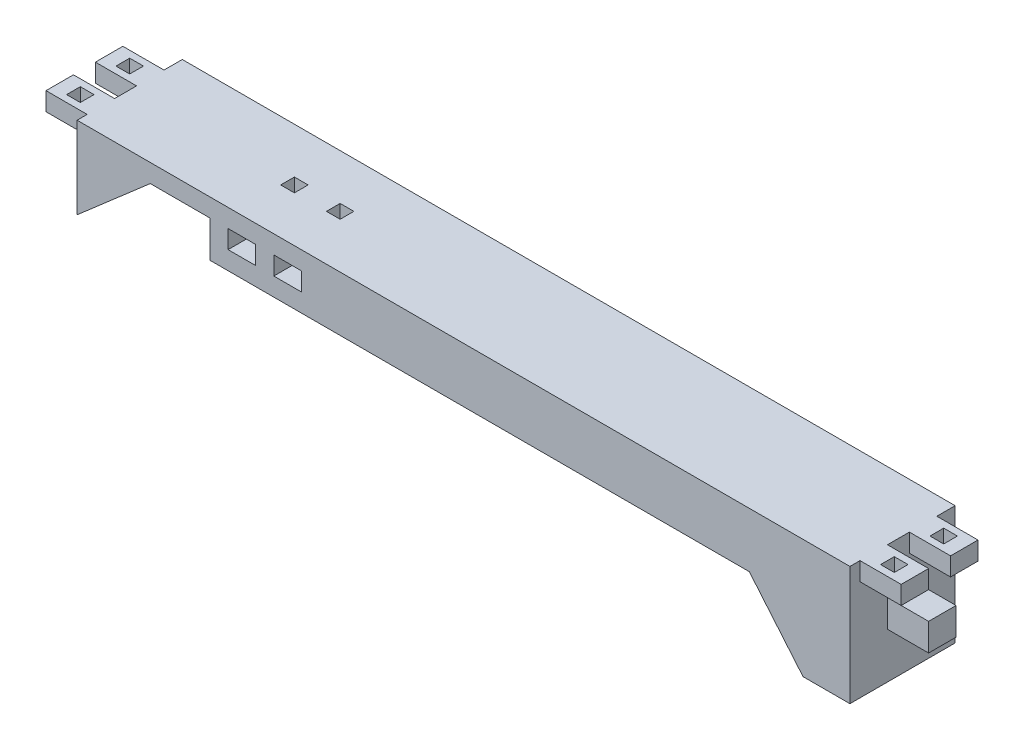
SolidWorks part; units mm, degrees
ref_plane "Front Plane" through (0, 0, 0) normal (0, 0, 1) x (1, 0, 0)
ref_plane "Top Plane" through (0, 0, 0) normal (0, 1, 0) x (1, 0, 0)
ref_plane "Right Plane" through (0, 0, 0) normal (1, 0, 0) x (0, 0, -1)
sketch "Sketch1" plane through (0, 0, 0) normal (0, 1, 0) x (1, 0, 0)
  line L1 (0, 0) -> (186.97, 0)
  line L2 (0, 0) -> (0, 23)
  line L3 (0, 23) -> (186.97, 23)
  line L4 (186.97, 0) -> (186.97, 23)
  dimension "D1" = 23
  dimension "D2" = 186.97
extrude "Boss-Extrude1" add sketch "Sketch1" along normal blind 4
sketch "Sketch2" plane through (0, 0, 0) normal (0, -1, 0) x (1, 0, 0)
  line L0 (186.97, -23) -> (0, -23) construction
  line L1 (177.97, 0) -> (167.97, 0)
  line L2 (177.97, 0) -> (177.97, -23)
  line L3 (177.97, -23) -> (167.97, -23)
  line L4 (167.97, 0) -> (167.97, -23)
  point P7 (0, 0)
  dimension "D1" = 10
extrude "Boss-Extrude2" add sketch "Sketch2" along normal blind 22
sketch "Sketch3" plane through (0, 0, 0) normal (0, -1, 0) x (1, 0, 0)
  line L0 (167.97, 0) -> (167.97, -23) construction
  line L1 (167.97, 0) -> (38.01, 0)
  line L2 (167.97, 0) -> (167.97, -8)
  line L3 (167.97, -8) -> (62.01, -8)
  line L4 (38.01, 0) -> (38.01, -8)
  line L5 (167.97, -23) -> (0, -23) construction
  line L7 (38.01, -8) -> (38.01, -23)
  line L8 (38.01, -23) -> (62.01, -23)
  line L9 (62.01, -8) -> (62.01, -23)
  dimension "D1" = 129.96
  dimension "D2" = 8
  dimension "D3" = 24
extrude "Boss-Extrude3" add sketch "Sketch3" along normal blind 8
chamfer "Chamfer1" distance 12 angle 50 1 edges at (167.97, -8, -4) first distance on face at (89.33, -8, -10.3333)
sketch "Sketch4" plane through (0, 0, 0) normal (0, -1, 0) x (1, 0, 0)
  line L6 (186.97, 0) -> (186.97, -23) construction
  line L11 (186.97, -8.2) -> (177.97, -8.2)
  line L12 (186.97, -8.2) -> (186.97, -13)
  line L13 (186.97, -13) -> (177.97, -13)
  line L14 (177.97, -8.2) -> (177.97, -13)
  line L15 (177.97, -23) -> (177.97, 0) construction
  line L17 (186.97, -23) -> (177.97, -23) construction
  line L18 (0, -23) -> (0, 0) construction
  line L19 (186.97, -23) -> (177.97, -23)
  line L20 (186.97, -23) -> (186.97, -19)
  line L21 (186.97, -19) -> (177.97, -19)
  line L22 (177.97, -23) -> (177.97, -19)
  line L23 (186.97, 0) -> (177.97, 0)
  line L24 (186.97, 0) -> (186.97, -2.2)
  line L25 (186.97, -2.2) -> (177.97, -2.2)
  line L26 (177.97, 0) -> (177.97, -2.2)
  line L27 (180.97, -14.5) -> (183.97, -14.5)
  line L28 (180.97, -14.5) -> (180.97, -17.5)
  line L29 (180.97, -17.5) -> (183.97, -17.5)
  line L30 (183.97, -14.5) -> (183.97, -17.5)
  line L31 (180.97, -3.7) -> (183.97, -3.7)
  line L32 (180.97, -3.7) -> (180.97, -6.7)
  line L33 (180.97, -6.7) -> (183.97, -6.7)
  line L34 (183.97, -3.7) -> (183.97, -6.7)
  line L35 (0, 0) -> (9, 0)
  line L36 (0, 0) -> (0, -2.2)
  line L37 (0, -2.2) -> (9, -2.2)
  line L38 (9, 0) -> (9, -2.2)
  line L39 (3, -3.7) -> (6, -3.7)
  line L40 (3, -3.7) -> (3, -6.7)
  line L41 (3, -6.7) -> (6, -6.7)
  line L42 (6, -3.7) -> (6, -6.7)
  line L44 (0, -8.2) -> (9, -8.2)
  line L45 (0, -8.2) -> (0, -13)
  line L46 (0, -13) -> (9, -13)
  line L47 (9, -8.2) -> (9, -13)
  line L48 (3, -14.5) -> (6, -14.5)
  line L49 (3, -14.5) -> (3, -17.5)
  line L50 (3, -17.5) -> (6, -17.5)
  line L51 (6, -14.5) -> (6, -17.5)
  line L52 (0, -23) -> (9, -23)
  line L53 (0, -23) -> (0, -19)
  line L54 (0, -19) -> (9, -19)
  line L55 (9, -23) -> (9, -19)
  dimension "D1" = 4.8
  dimension "D2" = 10
  dimension "D3" = 6
  dimension "D4" = 6
  dimension "D5" = 3
  dimension "D6" = 3
  dimension "D7" = 3
  dimension "D8" = 1.5
  dimension "D9" = 3
  dimension "D10" = 3
  dimension "D11" = 3
  dimension "D12" = 1.5
  dimension "D13" = 9
  dimension "D14" = 3
  dimension "D15" = 3
  dimension "D16" = 3
  dimension "D17" = 1.5
  dimension "D18" = 1.5
  dimension "D19" = 4.8
  dimension "D20" = 3
  dimension "D21" = 3
  dimension "D22" = 1.5
  dimension "D23" = 3
  dimension "D24" = 1.5
extrude "Cut-Extrude1" cut sketch "Sketch4" against normal up to next
sketch "Sketch5" plane through (177.97, 0, 0) normal (1, 0, 0) x (0, 0, -1)
  line L0 (8.2, 0) -> (2.2, 0) construction
  line L1 (8.2, -6) -> (14.2, -6)
  line L2 (8.2, -6) -> (8.2, -12)
  line L3 (8.2, -12) -> (14.2, -12)
  line L4 (14.2, -6) -> (14.2, -12)
  line L5 (2.2, 4) -> (2.2, 0) construction
  dimension "D1" = 6
  dimension "D2" = 6
  dimension "D3" = 6
  dimension "D4" = 6
extrude "Boss-Extrude4" add sketch "Sketch5" along normal blind 9
sketch "Sketch6" plane through (0, 0, -23) normal (0, 0, -1) x (-1, 0, 0)
  line L0 (-177.97, 4) -> (-9, 4) construction
  line L1 (-58.01, 0) -> (-52.01, 0)
  line L2 (-58.01, 0) -> (-58.01, -4)
  line L3 (-58.01, -4) -> (-52.01, -4)
  line L4 (-52.01, 0) -> (-52.01, -4)
  line L5 (-62.01, -8) -> (-62.01, 0) construction
  line L7 (-48.01, 0) -> (-42.01, 0)
  line L8 (-48.01, 0) -> (-48.01, -4)
  line L9 (-48.01, -4) -> (-42.01, -4)
  line L10 (-42.01, 0) -> (-42.01, -4)
  dimension "D1" = 6
  dimension "D2" = 4
  dimension "D3" = 4
  dimension "D4" = 4
  dimension "D5" = 6
  dimension "D6" = 4
extrude "Cut-Extrude2" cut sketch "Sketch6" against normal up to next
sketch "Sketch7" plane through (0, 4, 0) normal (0, 1, 0) x (1, 0, 0)
  line L0 (177.97, 23) -> (9, 23) construction
  line L1 (43.51, 13) -> (46.51, 13)
  line L2 (43.51, 13) -> (43.51, 10)
  line L3 (43.51, 10) -> (46.51, 10)
  line L4 (46.51, 13) -> (46.51, 10)
  line L5 (38.01, 0) -> (38.01, 23) construction
  line L7 (53.51, 13) -> (56.51, 13)
  line L8 (53.51, 13) -> (53.51, 10)
  line L9 (53.51, 10) -> (56.51, 10)
  line L10 (56.51, 13) -> (56.51, 10)
  dimension "D1" = 10
  dimension "D2" = 3
  dimension "D3" = 5.5
  dimension "D4" = 3
  dimension "D5" = 3
  dimension "D6" = 7
extrude "Cut-Extrude3" cut sketch "Sketch7" against normal up to next
sketch "Sketch8" plane through (0, 0, 0) normal (0, -1, 0) x (1, 0, 0)
  line L0 (38.01, -23) -> (9, -23) construction
  line L1 (9, 0) -> (25, 0)
  line L2 (9, 0) -> (9, -23)
  line L3 (9, -23) -> (25, -23)
  line L4 (25, 0) -> (25, -23)
  dimension "D1" = 16
extrude "Boss-Extrude5" add sketch "Sketch8" along normal blind 14
chamfer "Chamfer2" distance 14 angle 49 1 edges at (25, -14, -11.5) first distance on face at (25, -7, -11.5)
